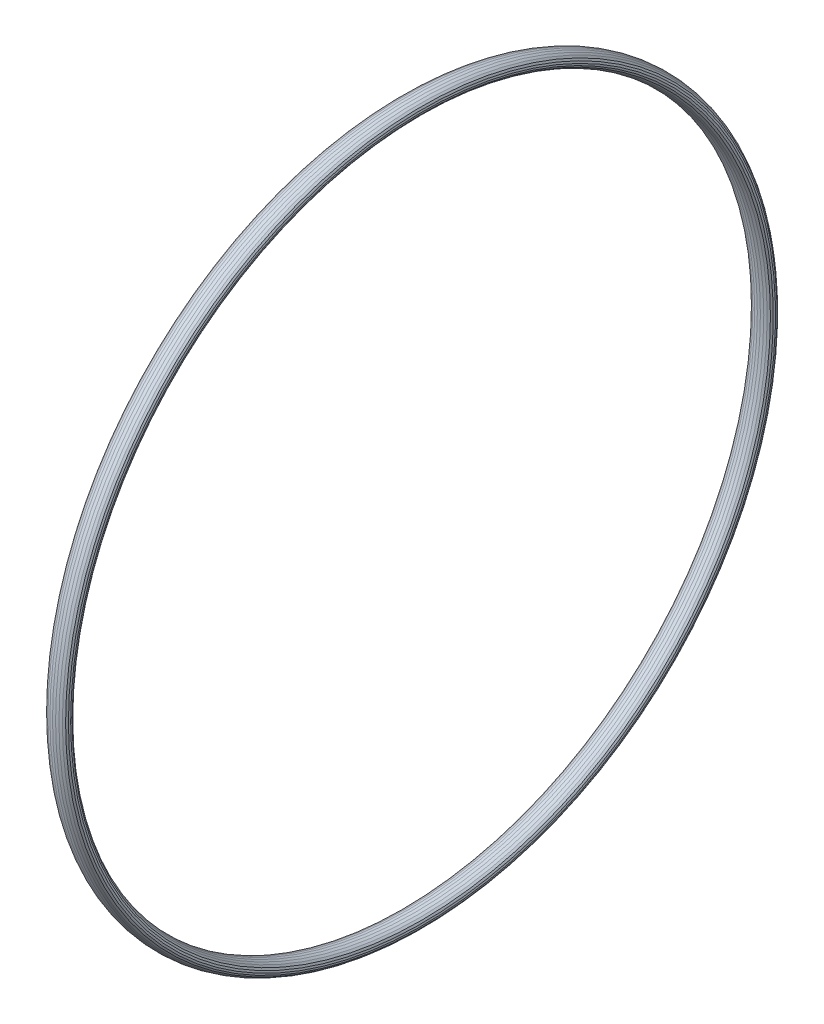
SolidWorks part; units mm, degrees
ref_plane "Front Plane" through (0, 0, 0) normal (0, 0, 1) x (1, 0, 0)
ref_plane "Top Plane" through (0, 0, 0) normal (0, 1, 0) x (1, 0, 0)
ref_plane "Right Plane" through (0, 0, 0) normal (1, 0, 0) x (0, 0, -1)
sketch "Tank_O_Ring Sketch" plane through (0, 0, 0) normal (0, 0, 1) x (1, 0, 0)
  line L0 (-1000, 0) -> (1000, 0) construction
  line L1 (24.375, 71.42) -> (24.939, 71.3713)
  line L2 (24.939, 71.3713) -> (25.4646, 71.2284)
  line L3 (25.4646, 71.2284) -> (25.9159, 71.0012)
  line L4 (25.9159, 71.0012) -> (26.2623, 70.705)
  line L5 (26.2623, 70.705) -> (26.48, 70.3601)
  line L6 (26.48, 70.3601) -> (26.5542, 69.99)
  line L7 (26.5542, 69.99) -> (26.48, 69.6199)
  line L8 (26.48, 69.6199) -> (26.2623, 69.275)
  line L9 (26.2623, 69.275) -> (25.9159, 68.9788)
  line L10 (25.9159, 68.9788) -> (25.4646, 68.7516)
  line L11 (25.4646, 68.7516) -> (24.939, 68.6087)
  line L12 (24.939, 68.6087) -> (24.375, 68.56)
  line L13 (24.375, 68.56) -> (23.811, 68.6087)
  line L14 (23.811, 68.6087) -> (23.2854, 68.7516)
  line L15 (23.2854, 68.7516) -> (22.8341, 68.9788)
  line L16 (22.8341, 68.9788) -> (22.4877, 69.275)
  line L17 (22.4877, 69.275) -> (22.27, 69.6199)
  line L18 (22.27, 69.6199) -> (22.1958, 69.99)
  line L19 (22.1958, 69.99) -> (22.27, 70.3601)
  line L20 (22.27, 70.3601) -> (22.4877, 70.705)
  line L21 (22.4877, 70.705) -> (22.8341, 71.0012)
  line L22 (22.8341, 71.0012) -> (23.2854, 71.2284)
  line L23 (23.2854, 71.2284) -> (23.811, 71.3713)
  line L24 (23.811, 71.3713) -> (24.375, 71.42)
revolve "Tank_O_Ring" add sketch "Tank_O_Ring Sketch" angle 360 about L0
ref_axis "Engine Axis" through (26.7721, 0, 0) along (-1, 0, 0)
